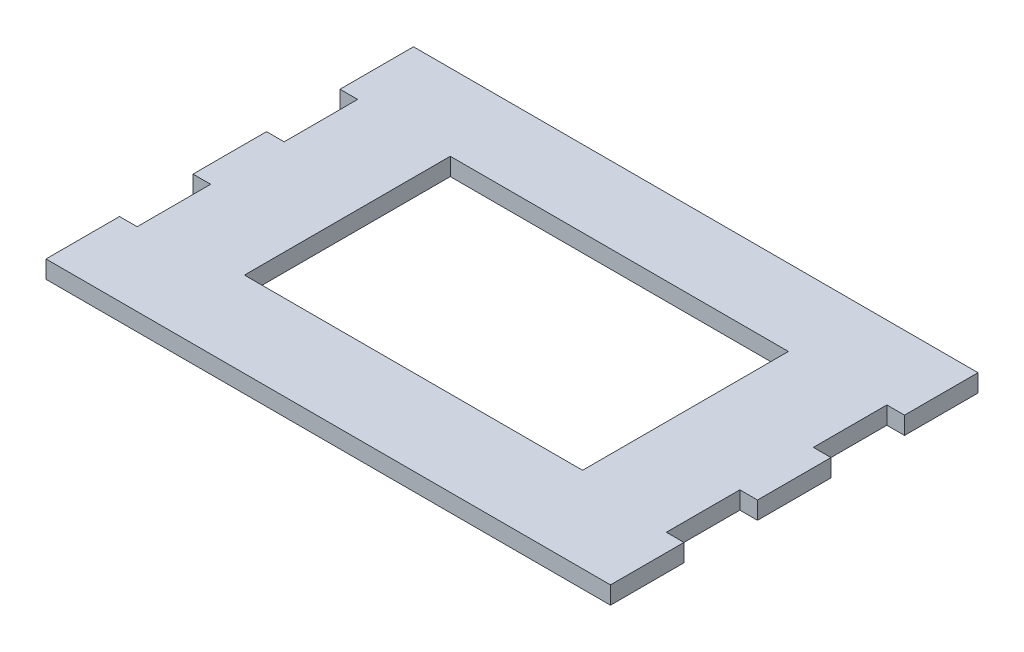
SolidWorks part; units mm, degrees
ref_plane "Front Plane" through (0, 0, 0) normal (0, 0, 1) x (1, 0, 0)
ref_plane "Top Plane" through (0, 0, 0) normal (0, 1, 0) x (1, 0, 0)
ref_plane "Right Plane" through (0, 0, 0) normal (1, 0, 0) x (0, 0, -1)
sketch "Sketch1" plane through (0, 0, 0) normal (0, 1, 0) x (1, 0, 0)
  line L0 (0, 0) -> (180, 0)
  line L1 (0, 100) -> (180, 100)
  line L2 (0, 0) -> (0, 100)
  line L4 (180, 0) -> (180, 100)
sketch "Sketch2" plane through (0, 0, 0) normal (0, 1, 0) x (1, 0, 0)
  line L1 (0, -6) -> (180, -6)
  line L2 (0, -6) -> (0, 106)
  line L3 (0, 106) -> (180, 106)
  line L4 (180, -6) -> (180, 106)
sketch "Sketch3" plane through (0, 0, 0) normal (0, 1, 0) x (1, 0, 0)
  line L1 (-6, -11) -> (186, -11)
  line L2 (-6, -11) -> (-6, 114)
  line L3 (-6, 114) -> (186, 114)
  line L4 (186, -11) -> (186, 114)
sketch "Sketch4" plane through (0, 0, 0) normal (0, 1, 0) x (1, 0, 0)
  line L0 (-6, 114) -> (-6, 89)
  line L1 (-6, -11) -> (-6, 114) construction
  line L2 (-6, 89) -> (0, 89)
  line L3 (0, 0) -> (0, 100) construction
  line L4 (0, 89) -> (0, 64)
  line L5 (0, 64) -> (-6, 64)
  line L6 (-6, 64) -> (-6, 39)
  line L7 (-6, 39) -> (0, 39)
  line L8 (0, 39) -> (0, 14)
  line L9 (0, 14) -> (-6, 14)
  line L10 (-6, 14) -> (-6, -11)
  line L11 (-6, -11) -> (-10, -11)
  line L12 (-10, -11) -> (-10, 114)
  line L13 (-10, 114) -> (-6, 114)
  line L26 (190, 114) -> (186, 114)
  line L27 (190, -11) -> (190, 114)
  line L28 (186, -11) -> (190, -11)
  line L29 (186, 14) -> (186, -11)
  line L30 (180, 14) -> (186, 14)
  line L31 (180, 39) -> (180, 14)
  line L32 (186, 39) -> (180, 39)
  line L33 (186, 64) -> (186, 39)
  line L34 (180, 64) -> (186, 64)
  line L35 (180, 89) -> (180, 64)
  line L36 (186, 89) -> (180, 89)
  line L37 (186, 114) -> (186, 89)
extrude "Boss-Extrude1" add sketch "Sketch3" along normal blind 6
extrude "Cut-Extrude1" cut sketch "Sketch4" along normal blind 6
ref_plane "Plane1" through (0, 6, 0) normal (0, 1, 0) x (1, 0, 0)
sketch "Sketch5" plane through (0, 6, 0) normal (0, 1, 0) x (1, 0, 0)
  line L0 (0, 0) -> (180, 0)
  line L1 (0, 100) -> (180, 100)
  line L2 (0, 0) -> (0, 100)
  line L4 (180, 0) -> (180, 100)
sketch "Sketch7" plane through (0, 6, 0) normal (0, 1, 0) x (1, 0, 0)
  line L1 (0, -6) -> (180, -6)
  line L2 (0, -6) -> (0, 106)
  line L3 (0, 106) -> (180, 106)
  line L4 (180, -6) -> (180, 106)
sketch "Sketch8" plane through (0, 0, 0) normal (0, 1, 0) x (1, 0, 0)
  line L4 (35, 23) -> (145, 23)
  line L5 (35, 23) -> (35, 83)
  line L6 (35, 83) -> (145, 83)
  line L7 (145, 23) -> (145, 83)
  line L8 (35, 23) -> (145, 83) construction
  line L9 (35, 83) -> (145, 23) construction
  point P0 (0, 0)
  point P6 (90, 53)
  point P7 (90, 53)
sketch "Sketch9" plane through (0, 0, 0) normal (0, 1, 0) x (1, 0, 0)
  line L1 (32.5, 88) -> (147.5, 88)
  line L2 (32.5, 88) -> (32.5, 18)
  line L3 (32.5, 18) -> (147.5, 18)
  line L4 (147.5, 88) -> (147.5, 18)
  line L5 (32.5, 88) -> (147.5, 18) construction
  line L6 (32.5, 18) -> (147.5, 88) construction
  point P0 (90, 53)
sketch "Sketch10" plane through (0, 0, 0) normal (0, 1, 0) x (1, 0, 0)
  line L1 (27, 93) -> (153, 93)
  line L2 (27, 93) -> (27, 13)
  line L3 (27, 13) -> (153, 13)
  line L4 (153, 93) -> (153, 13)
  line L5 (27, 93) -> (153, 13) construction
  line L6 (27, 13) -> (153, 93) construction
  point P0 (90, 53)
  point P6 (0, 0)
extrude "Cut-Extrude2" cut sketch "Sketch9" along normal blind 47
